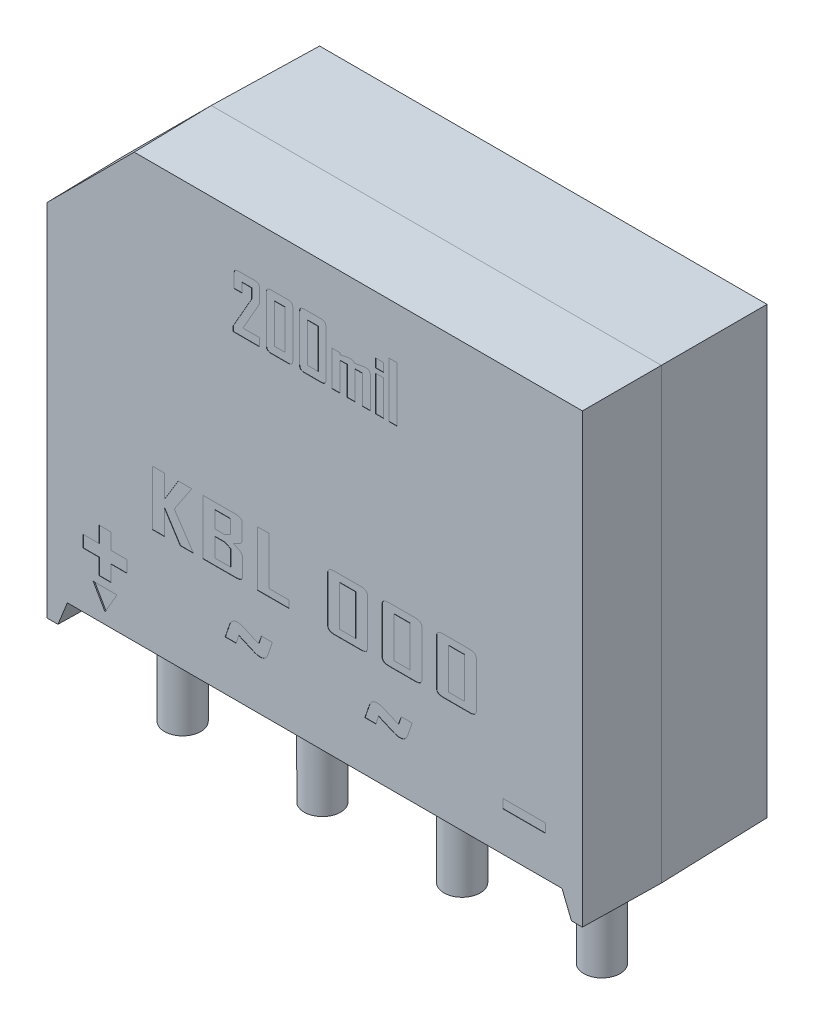
SolidWorks part; units mm, degrees
ref_plane "Спереди" through (0, 0, 0) normal (0, 0, 1) x (1, 0, 0)
ref_plane "Сверху" through (0, 0, 0) normal (0, 1, 0) x (1, 0, 0)
ref_plane "Справа" through (0, 0, 0) normal (1, 0, 0) x (0, 0, -1)
sketch "Sketch1" plane through (0, 0, 0) normal (0, 0, 1) x (1, 0, 0)
  line L0 (0, 16.3) -> (0, 0) construction
  line L1 (-2.16, 16.3) -> (17.4, 16.3)
  line L2 (-2.16, 16.3) -> (-2.16, 0)
  line L3 (-2.16, 0) -> (17.4, 0)
  line L4 (17.4, 16.3) -> (17.4, 0)
  line L5 (-2.16, 16.3) -> (17.4, 0) construction
  point P7 (7.62, 8.15)
  dimension "L" = 19.56
  dimension "H" = 16.3
  dimension "PIN_L1_H" = 0
  dimension "PIN_START" = 7.62
extrude "BODY_MAIN" add sketch "Sketch1" along normal blind 2.82 and the other way blind 3.91
sketch "Sketch18" plane through (0, 0, 2.82) normal (0, 0, 1) x (1, 0, 0)
  line L0 (7.62, 0) -> (7.62, 16.3) construction
  line L1 (-2.16, 0) -> (17.4, 0) construction
  line L2 (16.5768, 0.8) -> (-1.3368, 0.8)
  line L3 (17.4, 16.3) -> (-2.16, 16.3) construction
  line L4 (-1.3368, 0.8) -> (-1.66, 0)
  line L5 (-1.66, 0) -> (-1.66, -1)
  line L6 (-1.66, -1) -> (16.9, -1)
  line L7 (7.62, 0) -> (7.62, -1) construction
  line L8 (-2.16, 16.3) -> (-2.16, 0) construction
  line L9 (16.5768, 0.8) -> (16.9, 0)
  line L10 (16.9, 0) -> (16.9, -1)
  point P14 (7.62, 0.8)
  dimension "D1" = 0.8
  dimension "D2" = 68
  dimension "D3" = 0.5
  dimension "D4" = 1
extrude "Cut-Extrude2" cut sketch "Sketch18" against normal through all
chamfer "BODY_Chamfer" distance 3.2 angle 45 1 edges at (-2.16, 16.3, -0.545)
chamfer "BODY_Chamfer1" distance 2.82 angle 1 7 edges at (9.22, 16.3, 2.82) (17.4, 8.15, 2.82) (-2.16, 6.55, 2.82) (16.7384, 0.4, 2.82) (7.62, 0.8, 2.82) (-1.4984, 0.4, 2.82) (-0.56, 14.7, 2.82)
chamfer "BODY_Chamfer2" distance 3.91 angle 1 9 edges at (17.15, 0, -3.91) (-1.91, 0, -3.91) (17.4, 8.15, -3.91) (9.22, 16.3, -3.91) (-2.16, 6.55, -3.91) (-1.4984, 0.4, -3.91) (7.62, 0.8, -3.91) (16.7384, 0.4, -3.91) (-0.56, 14.7, -3.91)
sketch "Sketch10" plane through (0, 0, 0) normal (0, 1, 0) x (1, 0, 0)
  circle A0 centre (0, 0) radius 0.66
  dimension "D1" = 1.32
sketch "Sketch12" plane through (0, 0, 0) normal (1, 0, 0) x (0, 0, -1)
  line L0 (0, 0) -> (0, -3.6)
  line L1 (0, 0) -> (0, 1.3)
  point P5 (0, 0.8)
  dimension "D1" = 3.6
sweep "PIN_straight" add profiles "Sketch10" path "Sketch12"
pattern_linear "PIN_straight_Pattern" count 4 spacing 5.08 along (1, 0, 0) of "PIN_straight"
sketch "Sketch17" plane through (0, 0, 0) normal (1, 0, 0) x (0, 0, -1)
  line L0 (1.3, -1.5) -> (7.51, -1.5)
  line L1 (0, 0) -> (0, -0.2)
  line L2 (3.91, -1.5) -> (3.91, 0.8682) construction
  line L3 (0, 0) -> (0, 1.3)
  arc A0 (1.3, -1.5) -> (0, -0.2) centre (1.3, -0.2) cw
  point P5 (3.91, 0.8682)
  dimension "D2" = 1.3
  dimension "D3" = 3.6
sweep "PIN_bent" [suppressed] add profiles "Sketch10<2>" path "Sketch17"
sketch "Sketch10<2>"
  dimension "D1" = 1.32
pattern_linear "PIN_bent_Pattern" [suppressed] count 4 spacing 5.08
sketch "Sketch5" plane through (0, 0, 2.82) normal (0, 0, 1) x (1, 0, 0)
  line L0 (-2.1108, 8.55) -> (-2.1108, 0.8492) construction
  line L1 (-2.1108, 16.2508) -> (17.3508, 16.2508) construction
  line L2 (-2.1108, 16.2508) -> (-2.1108, 0.8492) construction
  line L3 (-2.1108, 0.8492) -> (17.3508, 0.8492) construction
  line L4 (17.3508, 16.2508) -> (17.3508, 0.8492) construction
  line L5 (-2.1108, 0.8492) -> (-2.1108, 4.6996) construction
  line L6 (-2.1108, 8.55) -> (17.3508, 8.55) construction
  line L7 (-2.1108, 16.2508) -> (-2.1108, 8.55) construction
  line L8 (-2.1108, 12.4004) -> (17.3508, 12.4004) construction
  line L9 (-2.1108, 4.6996) -> (17.3508, 4.6996) construction
  line L10 (17.3508, 16.2508) -> (1.0604, 16.2508) construction
  line L12 (-2.1108, 2.7744) -> (17.3508, 2.7744) construction
  line L13 (17.3508, 0) -> (17.3508, 16.2508) construction
  line L14 (-2.1108, 13.0796) -> (-2.1108, 0) construction
  line L15 (0, 0) -> (0, 2.7744) construction
  line L16 (-1.25, 2.7744) -> (-1.25, 0.8492) construction
  line L17 (1.25, 0.8492) -> (1.25, 2.7744) construction
  line L18 (-1.25, 2.7744) -> (1.25, 2.7744) construction
  line L20 (-1.25, 1.8118) -> (1.25, 1.8118) construction
  line L21 (3.83, 1.8118) -> (6.33, 1.8118) construction
  line L22 (8.91, 1.8118) -> (11.41, 1.8118) construction
  line L23 (13.99, 1.8118) -> (16.49, 1.8118) construction
  line L25 (-1.37, 0.8492) -> (16.61, 0.8492) construction
  text T0 "KBL 000" font "Agency FB" height 2
  text T1 "200mil" font "Agency FB" height 2
  text T2 "+" font "Agency FB" height 3
  text T3 "_" font "Agency FB" height 3
  text T4 "~" font "Agency FB" height 3
  text T5 "~" font "Agency FB" height 3
  point P17 (0, 0)
  dimension "D2" = 5.08
  dimension "D3" = 2.5
extrude "text" cut sketch "Sketch5" against normal blind 0.01
sketch "Sketch16" plane through (0, 0, 2.82) normal (0, 0, 1) x (1, 0, 0)
  line L0 (0, 0) -> (0, 1.7492) construction
  line L2 (0, 1.2492) -> (0.433, 1.9992)
  line L3 (0.433, 1.9992) -> (-0.433, 1.9992)
  line L4 (-0.433, 1.9992) -> (0, 1.2492)
  line L5 (-1.37, 0.8492) -> (16.61, 0.8492) construction
  circle A0 centre (0, 1.7492) radius 0.25 construction
  dimension "D1" = 0.5
  dimension "D2" = 0.9
extrude "pin1_mark" cut sketch "Sketch16" against normal blind 0.04
equation "\"PART_L\"= 19.56mm"
equation "\"PART_H\"= 16.3mm"
equation "\"PART_W\"= 6.73mm"
equation "\"PART_Camfer\"= 3.2mm"
equation "\"PART_PINS\"=4"
equation "\"DUMMY\"= 0"
equation "\"D1@BODY_MAIN\"= ( ( \"PIN_D\" / 2 ) + \"PIN_OFFSET\" )"
equation "\"L@Sketch1\" = \"PART_L\""
equation "\"H@Sketch1\" = \"PART_H\""
equation "\"D2@BODY_MAIN\"= \"PART_W\" - ((\"PIN_D\"/2) + \"PIN_OFFSET\")"
equation "\"PIN_D\"= 1.32mm"
equation "\"DUMMY2\"= 0"
equation "\"DUMMY3\"= 0"
equation "\"PIN_PITCH\"= 200mil"
equation "\"PIN_OFFSET\"= 2.16mm"
equation "\"D1@BODY_Chamfer\" = \"PART_Camfer\""
equation "\"PIN_START@Sketch1\" =  ( \"PIN_PITCH\" *  ( \"PART_PINS\" / 2 )  )  -  ( \"PIN_PITCH\" / 2 ) "
equation "\"PIN_L1_H\"= 0mm"
equation "\"PIN_L1_H@Sketch1\" = \"PIN_L1_H\""
equation "\"PIN_L2_H\"= \"PCB_clearance\" + \"PCB_thickness\" + \"PCB_rear\""
equation "\"DUMMY0\"= 0"
equation "\"DUMMY1\"= 0"
equation "\"PCB_clearance\"= 1mm"
equation "\"PCB_thickness\"= 1.6mm"
equation "\"PCB_rear\"= 1mm"
equation "\"D1@Sketch12\"=\"PIN_L2_H\""
equation "\"D3@Sketch17\"=\"PIN_L2_H\""
equation "\"D2@Sketch5\"=\"PIN_PITCH\""
equation "\"D1@Sketch5\"=\"PART_PINS\""
equation "\"D1@BODY_Chamfer2\"=\"D2@BODY_MAIN\""
equation "\"D1@BODY_Chamfer1\"=\"D1@BODY_MAIN\""
equation "\"D1@Sketch10\"=\"PIN_D\""
equation "\"D3@PIN_straight_Pattern\" = \"PIN_PITCH\""
equation "\"D1@PIN_straight_Pattern\" = \"PART_PINS\""
equation "\"D3@PIN_bent_Pattern\"=\"PIN_PITCH\""
equation "\"D1@PIN_bent_Pattern\"=\"PART_PINS\""
